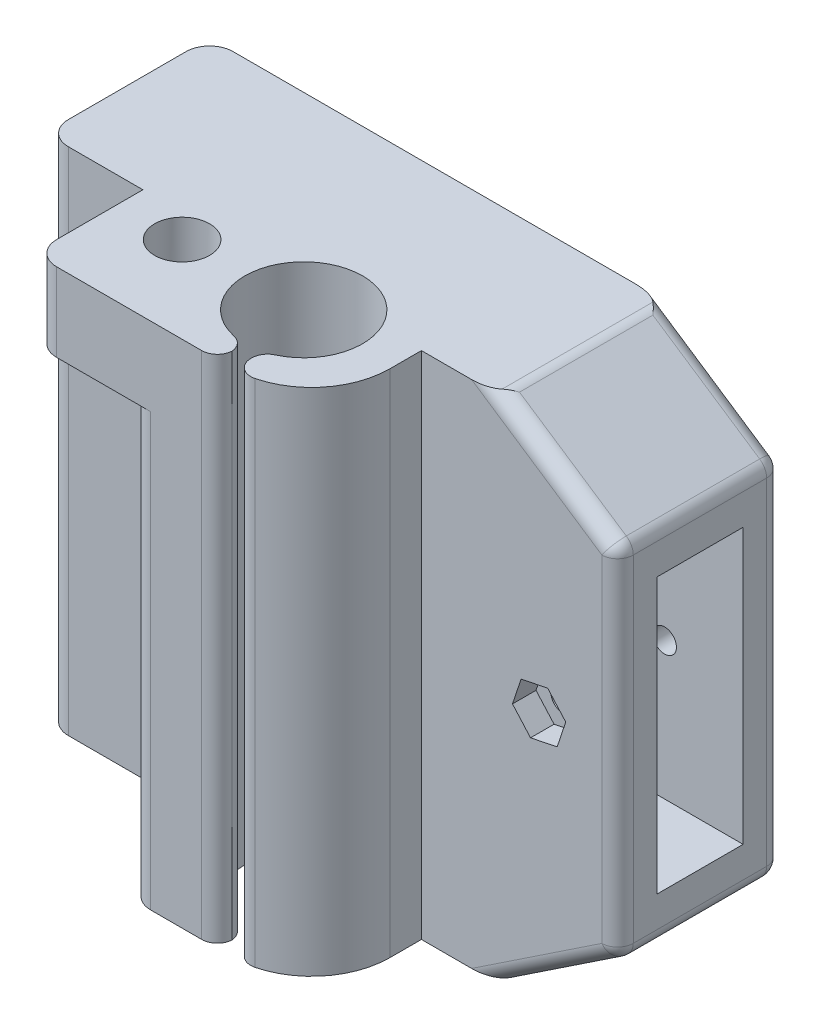
SolidWorks part; units mm, degrees
ref_plane "Front Plane" through (0, 0, 0) normal (0, 0, 1) x (1, 0, 0)
ref_plane "Top Plane" through (0, 0, 0) normal (0, 1, 0) x (1, 0, 0)
ref_plane "Right Plane" through (0, 0, 0) normal (1, 0, 0) x (0, 0, -1)
sketch "Sketch1" plane through (0, 0, 0) normal (0, 1, 0) x (1, 0, 0)
  line L1 (0, 0) -> (48, 0)
  line L2 (0, 0) -> (0, 35)
  line L3 (0, 35) -> (48, 35)
  line L4 (48, 0) -> (48, 35)
  dimension "D1" = 48
  dimension "D2" = 35
extrude "Boss-Extrude1" add sketch "Sketch1" along normal blind 65
sketch "Sketch2" plane through (0, 65, 0) normal (0, 1, 0) x (1, 0, 0)
  line L0 (0, 0) -> (48, 0) construction
  line L4 (48, 0) -> (48, 35) construction
  circle A0 centre (36, 11) radius 7.5
  circle A1 centre (20.5, 11) radius 3.5
  dimension "D1" = 15
  dimension "D5" = 7
  dimension "D6" = 15.5
  dimension "D2" = 11
  dimension "D3" = 12
  dimension "D4" = 11
extrude "Cut-Extrude1" cut sketch "Sketch2" against normal through all
sketch "Sketch3" plane through (0, 0, 0) normal (-1, 0, 0) x (0, 0, 1)
  line L0 (-35, 65) -> (0, 65) construction
  line L1 (0, 0) -> (-14, 0)
  line L2 (0, 0) -> (0, 65)
  line L3 (0, 65) -> (-14, 65)
  line L4 (-14, 0) -> (-14, 65)
  dimension "D1" = 21
extrude "Cut-Extrude2" cut sketch "Sketch3" against normal blind 12.5
sketch "Sketch4" plane through (12.5, 0, 0) normal (-1, 0, 0) x (0, 0, 1)
  line L0 (0, 0) -> (0, 65) construction
  line L1 (-14, 0) -> (0, 0)
  line L2 (-14, 0) -> (-14, 55)
  line L3 (-14, 55) -> (0, 55)
  line L4 (0, 0) -> (0, 55)
  line L5 (0, 65) -> (-14, 65) construction
  dimension "D1" = 10
extrude "Cut-Extrude3" cut sketch "Sketch4" against normal blind 12
sketch "Sketch5" plane through (0, 0, 0) normal (0, -1, 0) x (1, 0, 0)
  line L1 (25.215, -14.5283) -> (25.9131, -8.6808)
  line L2 (25.9131, -8.6808) -> (21.198, -5.1525)
  line L3 (21.198, -5.1525) -> (15.785, -7.4717)
  line L4 (15.785, -7.4717) -> (15.0869, -13.3192)
  line L5 (15.0869, -13.3192) -> (19.802, -16.8475)
  line L6 (19.802, -16.8475) -> (25.215, -14.5283)
  circle A0 centre (20.5, -11) radius 5.1 construction
  dimension "D1" = 10.2
extrude "Cut-Extrude4" cut sketch "Sketch5" against normal blind 60
sketch "Sketch6" plane through (0, 0, 0) normal (0, -1, 0) x (-1, 0, 0)
  circle A0 centre (-20.5, 11) radius 7.25
  dimension "D1" = 14.5
extrude "Cut-Extrude5" cut sketch "Sketch6" against normal blind 5
sketch "Sketch7" plane through (0, 0, 0) normal (-1, 0, 0) x (0, 0, 1)
  line L0 (-35, 65) -> (-35, 0) construction
  line L1 (-30, 50) -> (-19, 50)
  line L2 (-30, 50) -> (-30, 15)
  line L3 (-30, 15) -> (-19, 15)
  line L4 (-19, 50) -> (-19, 15)
  line L5 (-14, 65) -> (-14, 0) construction
  line L6 (-35, 0) -> (-14, 0) construction
  line L7 (-35, 65) -> (-14, 65) construction
  dimension "D1" = 5
  dimension "D2" = 5
  dimension "D3" = 15
  dimension "D4" = 15
extrude "Cut-Extrude6" cut sketch "Sketch7" against normal through all
sketch "Sketch8" plane through (0, 0, 0) normal (-1, 0, 0) x (0, 0, 1)
  line L0 (-35, 65) -> (-14, 65) construction
  line L1 (-35, 65) -> (-35, 0) construction
  line L3 (-35, 0) -> (-14, 0) construction
  circle A0 centre (-24.5, 58) radius 4
  circle A1 centre (-24.5, 7) radius 4
  dimension "D1" = 8
  dimension "D2" = 8
  dimension "D3" = 7
  dimension "D4" = 10.5
  dimension "D5" = 10.5
  dimension "D6" = 7
extrude "Cut-Extrude7" cut sketch "Sketch8" against normal blind 30
sketch "Sketch9" plane through (0, 0, -35) normal (0, 0, -1) x (-1, 0, 0)
  line L0 (-48, 0) -> (0, 0) construction
  line L1 (-43, 50) -> (-5, 50)
  line L2 (-43, 50) -> (-43, 15)
  line L3 (-43, 15) -> (-5, 15)
  line L4 (-5, 50) -> (-5, 15)
  line L5 (0, 65) -> (0, 0) construction
  line L6 (-48, 65) -> (-48, 0) construction
  line L7 (-48, 65) -> (0, 65) construction
  dimension "D1" = 15
  dimension "D2" = 5
  dimension "D3" = 5
  dimension "D4" = 15
extrude "Cut-Extrude8" cut sketch "Sketch9" against normal blind 10
fillet "Fillet1" radius 3 4 edges at (0, 32.5, -35) (24.5, 27.5, 0) (12.5, 60, 0) (0, 32.5, -14)
sketch "Sketch11" plane through (48, 0, 0) normal (1, 0, 0) x (0, 0, -1)
  line L0 (0, 65) -> (35, 65) construction
  line L1 (35, 0) -> (14, 0)
  line L2 (35, 0) -> (35, 65)
  line L3 (35, 65) -> (14, 65)
  line L4 (14, 0) -> (14, 65)
  dimension "D1" = 21
extrude "Boss-Extrude2" add sketch "Sketch11" along normal blind 25
fillet "Fillet2" radius 10 1 edges at (48, 32.5, 0)
sketch "Sketch12" plane through (0, 65, 0) normal (0, 1, 0) x (1, 0, 0)
  line L0 (36, 0) -> (36, 3.5)
  line L1 (15.5, 0) -> (38, 0) construction
  line L2 (36, 3.5) -> (38, 3.7716)
  line L3 (38, 3.7716) -> (38, 0)
  line L4 (38, 0) -> (36, 0)
  circle A0 centre (36, 11) radius 7.5 construction
  dimension "D1" = 2
extrude "Cut-Extrude9" cut sketch "Sketch12" against normal through all
fillet "Fillet3" radius 2 4 edges at (38, 32.5, 0) (36, 32.5, 0) (36, 32.5, -3.5) (38, 32.5, -3.7716)
sketch "Sketch13" plane through (73, 0, 0) normal (1, 0, 0) x (0, 0, -1)
  line L0 (35, 0) -> (35, 65) construction
  line L1 (19, 15) -> (30, 15)
  line L2 (19, 15) -> (19, 50)
  line L3 (19, 50) -> (30, 50)
  line L4 (30, 15) -> (30, 50)
  line L5 (14, 65) -> (14, 0) construction
  line L6 (14, 0) -> (35, 0) construction
  line L7 (35, 65) -> (14, 65) construction
  point P8 (24.5, 0)
  dimension "D1" = 5
  dimension "D2" = 5
  dimension "D3" = 15
  dimension "D4" = 15
extrude "Cut-Extrude10" cut sketch "Sketch13" against normal through all
sketch "Sketch14" plane through (0, 0, -35) normal (0, 0, -1) x (-1, 0, 0)
  line L0 (-73, 65) -> (-58, 65)
  line L1 (-73, 65) -> (-3, 65) construction
  line L2 (-58, 65) -> (-73, 55)
  line L3 (-73, 0) -> (-73, 65) construction
  line L4 (-73, 55) -> (-73, 65)
  line L5 (-73, 0) -> (-58, 0)
  line L6 (-73, 0) -> (-3, 0) construction
  line L7 (-58, 0) -> (-73, 10)
  line L8 (-73, 10) -> (-73, 0)
  dimension "D1" = 15
  dimension "D2" = 10
  dimension "D3" = 10
  dimension "D4" = 15
extrude "Cut-Extrude11" cut sketch "Sketch14" against normal through all
sketch "Sketch16" plane through (0, 0, -35) normal (0, 0, -1) x (-1, 0, 0)
  line L0 (-58, 0) -> (-3, 0) construction
  line L1 (-73, 10) -> (-73, 55) construction
  circle A0 centre (-63, 32.5) radius 1.5
  dimension "D3" = 3
  dimension "D1" = 32.5
  dimension "D2" = 10
extrude "Cut-Extrude13" cut sketch "Sketch16" against normal through all
sketch "Sketch17" plane through (0, 0, -14) normal (0, 0, 1) x (1, 0, 0)
  line L1 (60.7002, 35.0906) -> (59.6066, 31.8036)
  line L2 (59.6066, 31.8036) -> (61.9064, 29.213)
  line L3 (61.9064, 29.213) -> (65.2998, 29.9094)
  line L4 (65.2998, 29.9094) -> (66.3934, 33.1964)
  line L5 (66.3934, 33.1964) -> (64.0936, 35.787)
  line L6 (64.0936, 35.787) -> (60.7002, 35.0906)
  circle A0 centre (63, 32.5) radius 3 construction
  dimension "D1" = 6
extrude "Cut-Extrude14" cut sketch "Sketch17" against normal blind 3
fillet "Fillet4" radius 2 10 edges at (65.5, 5, -35) (65.5, 5, -14) (65.5, 60, -35) (65.5, 60, -14) (73, 32.5, -14) (73, 32.5, -35) (58, 0, -24.5) (73, 10, -24.5) (73, 55, -24.5) (58, 65, -24.5)
